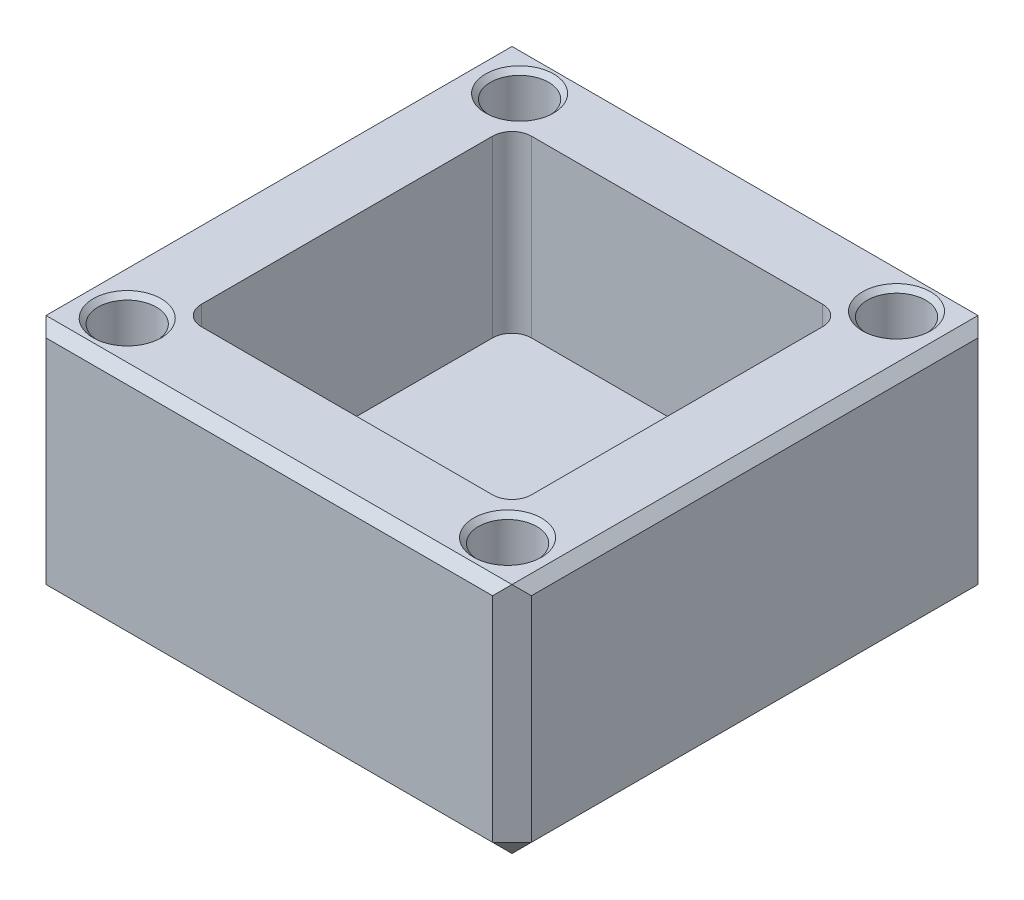
SolidWorks part; units mm, degrees
material "ABS PC"
ref_plane "Front Plane" through (0, 0, 0) normal (0, 0, 1) x (1, 0, 0)
ref_plane "Top Plane" through (0, 0, 0) normal (0, 1, 0) x (1, 0, 0)
ref_plane "Right Plane" through (0, 0, 0) normal (1, 0, 0) x (0, 0, -1)
sketch "Sketch1" plane through (0, 0, 0) normal (0, 1, 0) x (1, 0, 0)
  line L1 (-25, 25) -> (25, 25)
  line L2 (-25, 25) -> (-25, -25)
  line L3 (-25, -25) -> (25, -25)
  line L4 (25, 25) -> (25, -25)
  line L5 (-25, 25) -> (25, -25) construction
  line L6 (-25, -25) -> (25, 25) construction
  point P0 (0, 0)
  dimension "D1" = 50
  dimension "D2" = 50
extrude "Boss-Extrude1" add sketch "Sketch1" along normal blind 25
sketch "Sketch2" plane through (0, 25, 0) normal (0, 1, 0) x (1, 0, 0)
  line L0 (-25, 25) -> (-25, -25) construction
  line L1 (-17, 17) -> (17, 17)
  line L2 (-17, 17) -> (-17, -17)
  line L3 (-17, -17) -> (17, -17)
  line L4 (17, 17) -> (17, -17)
  line L5 (-17, 17) -> (17, -17) construction
  line L6 (-17, -17) -> (17, 17) construction
  line L8 (25, 25) -> (-25, 25) construction
  circle A0 centre (-19.5684, -20.0665) radius 3
  circle A1 centre (-19.4102, 20.1923) radius 3
  circle A2 centre (19.5919, -20.0467) radius 3
  circle A3 centre (19.434, 20.1742) radius 3
  point P0 (0, 0)
  point P6 (-17, 0)
  point P15 (0, 0)
  point P20 (0, 0)
  point P21 (0, 0)
  point P22 (0, 0)
  dimension "D3" = 4
  dimension "D1" = 8
  dimension "D2" = 8
  dimension "D4" = 4
  dimension "D5" = 4
  dimension "D6" = 4
extrude "Cut-Extrude1" cut sketch "Sketch2" against normal blind 18 contours L2 L1 L4 L3 | A0 | A1 | A3 | A2
chamfer "Chamfer1" distance 2 8 edges at (0, 0, -25) (-25, 12.5, -25) (-25, 0, 0) (25, 12.5, -25) (25, 0, 0) (25, 12.5, 25) (0, 0, 25) (-25, 12.5, 25)
chamfer "Chamfer2" distance 1 4 edges at (-25, 25, 0) (0, 25, -25) (0, 25, 25) (25, 25, 0)
fillet "Fillet1" radius 2 4 edges at (-17, 16, 17) (17, 16, 17) (17, 16, -17) (-17, 16, -17)
chamfer "Chamfer3" distance 0.5 angle 45 4 edges at (19.434, 25, -17.1742) (-19.4102, 25, -17.1923) (-19.5684, 25, 23.0665) (19.5919, 25, 23.0467)
